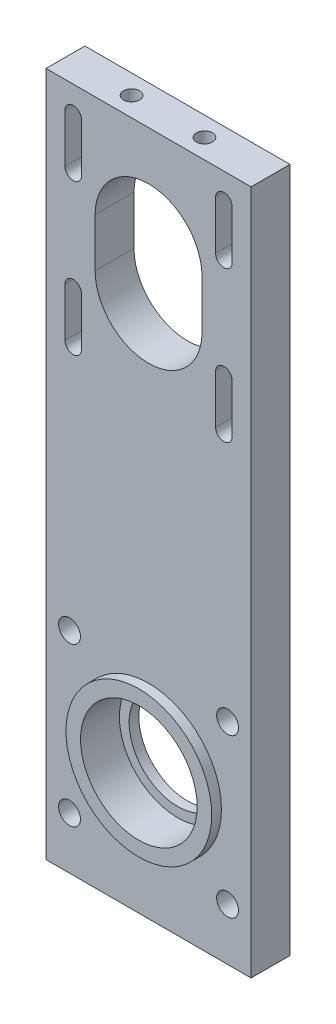
SolidWorks part; units mm, degrees
material "6061-T6 (SS)"
ref_plane "前基準面" through (0, 0, 0) normal (0, 0, 1) x (1, 0, 0)
ref_plane "上基準面" through (0, 0, 0) normal (0, 1, 0) x (1, 0, 0)
ref_plane "右基準面" through (0, 0, 0) normal (1, 0, 0) x (0, 0, -1)
sketch "草圖1" plane through (0, 0, 0) normal (0, 0, 1) x (1, 0, 0)
  line L1 (-21.1, -30) -> (21.1, -30)
  line L2 (-21.1, -30) -> (-21.1, 30)
  line L3 (-21.1, 30) -> (21.1, 30)
  line L4 (21.1, -30) -> (21.1, 30)
  line L5 (-21.1, -30) -> (21.1, 30) construction
  line L6 (-21.1, 30) -> (21.1, -30) construction
  point P0 (0, 0)
  dimension "D1" = 42.2
  dimension "D2" = 60
extrude "填料-伸長1" add sketch "草圖1" along normal mid plane 8
sketch "草圖5" plane through (0, 0, 4) normal (0, 0, 1) x (1, 0, 0)
  circle A0 centre (0, -3) radius 15
  dimension "D1" = 30
  dimension "D2" = 3
extrude "填料-伸長3" add sketch "草圖5" along normal blind 2
sketch "草圖6" plane through (0, 0, 6) normal (0, 0, 1) x (1, 0, 0)
  circle A0 centre (0, -3) radius 10
  dimension "D1" = 20
  dimension "D2" = 3
extrude "除料-伸長3" cut sketch "草圖6" against normal through all
sketch "草圖7" plane through (0, 0, 6) normal (0, 0, 1) x (1, 0, 0)
  circle A0 centre (0, -3) radius 12
  dimension "D1" = 24
  dimension "D2" = 3
extrude "除料-伸長4" cut sketch "草圖7" against normal blind 8
sketch "草圖8" plane through (0, 30, 0) normal (0, 1, 0) x (1, 0, 0)
  line L1 (-21.1, 4) -> (21.1, 4)
  line L2 (-21.1, 4) -> (-21.1, -4)
  line L3 (-21.1, -4) -> (21.1, -4)
  line L4 (21.1, 4) -> (21.1, -4)
extrude "填料-伸長4" add sketch "草圖8" along normal blind 81
sketch "草圖9" plane through (0, 0, -4) normal (0, 0, -1) x (-1, 0, 0)
  line L0 (0, 111) -> (0, 90) construction
  line L1 (-21.1, 111) -> (21.1, 111) construction
  line L2 (0, 90) -> (0, 80) construction
  line L3 (11, 90) -> (11, 80)
  line L4 (-11, 90) -> (-11, 80)
  arc A1 (11, 90) -> (-11, 90) centre (0, 90) ccw
  arc A2 (-11, 80) -> (11, 80) centre (0, 80) ccw
  point P5 (0, 85)
  dimension "D1" = 22
  dimension "D2" = 21
  dimension "D3" = 10
extrude "除料-伸長5" cut sketch "草圖9" against normal through all
hole_wizard "M3 凹頭蓋螺釘的柱孔7" positions "草圖10" profile "草圖11" size "M3" standard "Ansi Metric" slot yes end condition through all
sketch "草圖10" plane through (0, 0, -4) normal (0, 0, 1) x (1, 0, 0)
  line L3 (15.5, 100.5) -> (-15.5, 100.5) construction
  line L4 (15.5, 100.5) -> (15.5, 69.5) construction
  line L5 (15.5, 69.5) -> (-15.5, 69.5) construction
  line L6 (-15.5, 100.5) -> (-15.5, 69.5) construction
  line L7 (15.5, 100.5) -> (-15.5, 69.5) construction
  line L8 (15.5, 69.5) -> (-15.5, 100.5) construction
  line L9 (0, 90) -> (0, 85) construction
  line L11 (15.5, 93.8) -> (15.5, 107.2) construction
  point P117 (15.5, 100.5)
  point P121 (15.5, 69.5)
  point P123 (-15.5, 100.5)
  point P125 (-15.5, 69.5)
  dimension "D1" = 13.4
  dimension "D2" = 31
  dimension "D3" = 5
sketch "草圖11" plane through (15.5, 100.5, -4) normal (1, 0, 0) x (0, 1, 0)
  line L0 (0, 0) -> (0, 10)
  line L1 (0, 10) -> (1.7, 10)
  line L3 (1.7, 10) -> (1.7, 3)
  line L4 (1.7, 3) -> (3.25, 3)
  line L5 (3.25, 3) -> (3.25, 0)
  line L7 (3.25, 0) -> (0, 0)
  line L11 (0, -6.35) -> (0, 107.95) construction
  dimension "貫穿孔直徑" = 3.4
  dimension "貫穿孔深度" = 10
  dimension "柱孔直徑" = 6.5
  dimension "柱孔深度" = 3
hole_wizard "M4 凹頭蓋螺釘的柱孔1" positions "草圖16" profile "草圖17" counterbore size "M4" standard "Ansi Metric" end condition through all
sketch "草圖16" plane through (0, 0, -4) normal (0, 0, -1) x (-1, 0, 0)
  line L1 (-16.2635, -19.2635) -> (16.2635, -19.2635) construction
  line L2 (-16.2635, -19.2635) -> (-16.2635, 13.2635) construction
  line L3 (-16.2635, 13.2635) -> (16.2635, 13.2635) construction
  line L4 (16.2635, -19.2635) -> (16.2635, 13.2635) construction
  line L5 (-16.2635, -19.2635) -> (16.2635, 13.2635) construction
  line L6 (-16.2635, 13.2635) -> (16.2635, -19.2635) construction
  point P1 (16.2635, 13.2635)
  point P122 (-16.2635, -19.2635)
  point P123 (-16.2635, 13.2635)
  point P124 (16.2635, -19.2635)
  point P137 (0, -3)
  dimension "D1" = 46
  dimension "D2" = 3
sketch "草圖17" plane through (-16.2635, 13.2635, -4) normal (1, 0, 0) x (0, 1, 0)
  line L0 (0, 0) -> (0, 10)
  line L1 (0, 10) -> (2.25, 10)
  line L3 (2.25, 10) -> (2.25, 4)
  line L4 (2.25, 4) -> (4, 4)
  line L5 (4, 4) -> (4, 0)
  line L7 (4, 0) -> (0, 0)
  line L11 (0, -6.35) -> (0, 107.95) construction
  dimension "貫穿孔直徑" = 4.5
  dimension "貫穿孔深度" = 10
  dimension "柱孔直徑" = 8
  dimension "柱孔深度" = 4
hole_wizard "M4x0.7 螺紋孔1" positions "草圖14" profile "草圖15" tap size "M4x0.7" standard "Ansi Metric"
sketch "草圖14" plane through (0, -30, 0) normal (0, -1, 0) x (-1, 0, 0)
  line L0 (10, 0) -> (-10, 0) construction
  point P0 (10, 0)
  point P1 (-10, 0)
  point P7 (0, 0)
  dimension "D1" = 20
sketch "草圖15" plane through (-10, -30, 0) normal (1, 0, 0) x (0, 0, -1)
  line L0 (0, 0) -> (0, 11.0914)
  line L1 (0, 11.0914) -> (1.65, 10.1)
  line L2 (1.65, 10.1) -> (1.65, 0)
  line L5 (1.65, 0) -> (0, 0)
  line L10 (0, 11.0914) -> (-1.65, 10.1) construction
  line L11 (0, -6.35) -> (0, 107.95) construction
  dimension "螺孔鑽直徑" = 3.3
  dimension "螺孔鑽深度" = 10.1
  dimension "導頭角度" = 118
hole_wizard "M4x0.7 螺紋孔2" positions "草圖19" profile "草圖20" tap size "M4x0.7" standard "Ansi Metric"
sketch "草圖19" plane through (0, 111, 0) normal (0, 1, 0) x (1, 0, 0)
  line L0 (-7.5, 0) -> (7.5, 0) construction
  line L2 (21.1, 4) -> (-21.1, 4) construction
  line L3 (21.1, -4) -> (21.1, 4) construction
  point P0 (-7.5, 0)
  point P2 (7.5, 0)
  point P13 (0, 4)
  point P14 (0, 0)
  point P15 (-7.5, -1.2363)
  point P18 (21.1, 0)
  dimension "D1" = 15
sketch "草圖20" plane through (-7.5, 111, 0) normal (1, 0, 0) x (0, 0, 1)
  line L0 (0, 0) -> (0, 8.9914)
  line L1 (0, 8.9914) -> (1.65, 8)
  line L2 (1.65, 8) -> (1.65, 0)
  line L5 (1.65, 0) -> (0, 0)
  line L10 (0, 8.9914) -> (-1.65, 8) construction
  line L11 (0, -6.35) -> (0, 107.95) construction
  dimension "螺孔鑽直徑" = 3.3
  dimension "螺孔鑽深度" = 8
  dimension "導頭角度" = 118
cosmetic thread "鑽孔螺紋1" parameters "D1"=8, "D2"=4
cosmetic thread "鑽孔螺紋2" parameters "D1"=8, "D2"=4
